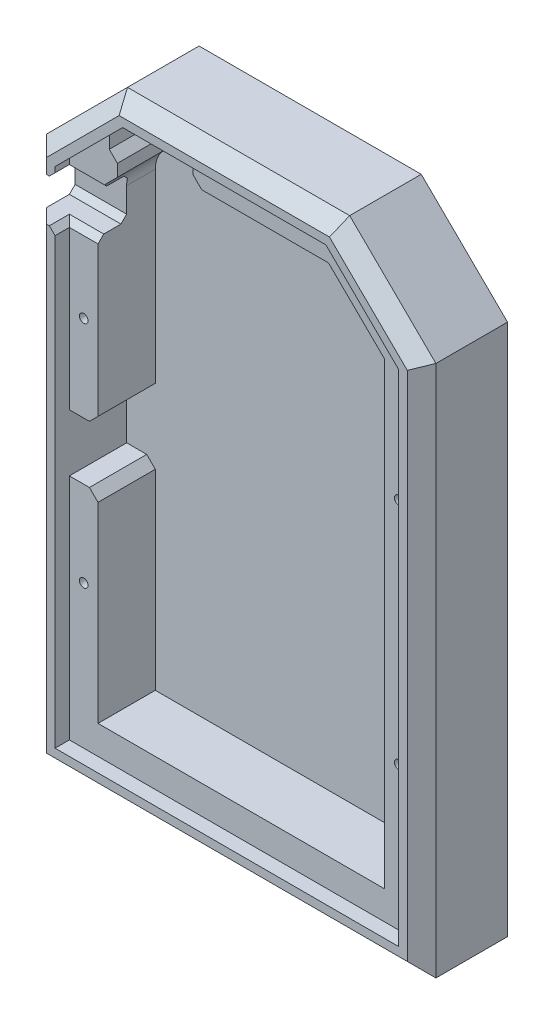
SolidWorks part; units mm, degrees
ref_plane "Front Plane" through (0, 0, 0) normal (1, 0, 0) x (0, 1, 0)
ref_plane "Top Plane" through (0, 0, 0) normal (0, 0, 1) x (0, 1, 0)
ref_plane "Right Plane" through (0, 0, 0) normal (0, 1, 0) x (-1, 0, 0)
sketch "Sketch1" plane through (0, 0, 0) normal (0, 0, 1) x (0, 1, 0)
  line L0 (175.9, 0) -> (199.5, -23.6)
  line L1 (0, 0) -> (175.9, 0)
  line L2 (0, 0) -> (0, -120)
  line L3 (0, -120) -> (174.5, -120)
  line L4 (199.5, -23.6) -> (199.5, -94.6)
  line L5 (199.5, -23.6) -> (199.5, -94.6)
  line L6 (199.5, -94.6) -> (174.5, -120)
  line L7 (205.2016, -100.2118) -> (177.851, -128)
  line L8 (-8, -128) -> (177.851, -128)
  line L9 (-8, 8) -> (-8, -128)
  line L10 (-8, 8) -> (179.2137, 8)
  line L11 (179.2137, 8) -> (205.1569, -17.9431)
  line L12 (207.5, -23.6) -> (207.5, -94.6)
  line L13 (207.5, -23.6) -> (207.5, -94.6)
  line L14 (177.851, -128) -> (207.5, -97.8766)
  line L15 (207.5, -97.8766) -> (207.5, -23.6)
  line L16 (179.2137, 8) -> (200.8013, -13.5876)
  line L17 (200.8013, -13.5876) -> (207.5, -20.2863)
  line L18 (207.5, -20.2863) -> (207.5, -23.6)
  line L19 (189.5, -90.5043) -> (170.3113, -110)
  line L20 (10, -110) -> (170.3113, -110)
  line L21 (10, -10) -> (10, -110)
  line L22 (10, -10) -> (171.7579, -10)
  line L23 (171.7579, -10) -> (189.5, -27.7421)
  line L24 (189.5, -27.7421) -> (189.5, -90.5043)
  line L25 (79.85, 0) -> (79.85, -12.2271)
  line L26 (192.373, -87.5853) -> (170.3113, -110) construction
  line L27 (189.5, -23.6) -> (189.5, -94.6) construction
  line L28 (171.7579, -10) -> (192.4289, -30.6711) construction
  line L29 (79.85, -12.2271) -> (99.85, -12.2271)
  line L30 (99.85, -12.2271) -> (99.85, 0)
  line L31 (79.85, 0) -> (99.85, 0)
  line L32 (187.7, -11.8) -> (169.825, -29.675)
  line L33 (169.825, -29.675) -> (183.3393, -43.1892)
  line L34 (183.3393, -43.1892) -> (199.5, -43.1892)
  line L35 (199.5, -43.1892) -> (199.5, -23.6)
  line L36 (50, -5) -> (50, -115) construction
  line L37 (130, -5) -> (130, -115) construction
  line L38 (130, -115) -> (50, -115) construction
  circle A0 centre (50, -5) radius 1.5
  circle A1 centre (130, -5) radius 1.5
  circle A2 centre (50, -115) radius 1.5
  circle A3 centre (130, -115) radius 1.5
  dimension "D5" = 3
  dimension "D1" = 120
  dimension "D2" = 8
  dimension "D3" = 50
  dimension "D4" = 5
  dimension "D6" = 10
  dimension "D7" = 80
  dimension "D8" = 20
  dimension "D9" = 30.15
  dimension "D10" = 5
extrude "Boss-Extrude1" add sketch "Sketch1" along normal blind 5 contours L34 L33 L32 L23 L22 L30 L29 L25 L21 L20 L19 L24 | L34 L24 L19 L20 L21 L22 L25 L1 L2 L3 L6 L5 A3 A2 A0 | L18 L17 L11 L10 L9 L8 L7 L14 L15 L12 L4 L5 L6 L3 L2 L1 L0 | L24 L34 L4 L0 L32 L23 | L32 L0 L1 L30 L22 L23 A1 | L33 L34 L24 L23 L32 | L22 L30 L1 L25 | L29 L30 L22 L25 | A0 | A1 | A3 | A2 region at (5.7866, 143.9357, 0) region at (28.013, 192.3485, 0) region at (5, 89.85, 0) region at (60.5328, 96.7361, 0) region at (31.5918, 181.6671, 0) region at (5, 77.5219, 0) region at (11.1136, 89.85, 0) region at (112.3184, 189.7101, 0) region at (5, 50, 0) region at (5, 130, 0) region at (115, 50, 0) region at (115, 130, 0)
extrude "Boss-Extrude2" add sketch "Sketch1<3>" along normal blind 25 contours L34 L24 L19 L20 L21 L22 L25 L1 L2 L3 L6 L5 A3 A2 A0 | L32 L0 L1 L30 L22 L23 A1 | L18 L17 L11 L10 L9 L8 L7 L14 L15 L12 L4 L5 L6 L3 L2 L1 L0 region at (5.7866, 143.9357, 0) region at (5, 77.5219, 0) region at (112.3184, 189.7101, 0)
sketch "Sketch1<3>" plane through (0, 0, 0) normal (0, 0, 1) x (0, 1, 0) same geometry as "Sketch1"
extrude "Boss-Extrude3" add sketch "Sketch1<4>" along normal blind 5 from surface contours L18 L17 L11 L10 L9 L8 L7 L14 L15 L12 L4 L5 L6 L3 L2 L1 L0 region at (112.3184, 189.7101, 0) starting at face at (35.0824, 133.4141, 25)
sketch "Sketch1<4>" plane through (0, 0, 0) normal (0, 0, 1) x (0, 1, 0) same geometry as "Sketch1"
chamfer "Chamfer1" distance 5 angle 45 6 edges at (6.1431, 193.3569, 30) (59.0814, 207.5, 30) (112.9383, 192.6755, 30) (-8, 85.6069, 30) (60, -8, 30) (128, 84.9255, 30)
chamfer "Chamfer2" distance 3 angle 45 6 edges at (10, 79.85, 15) (10, 99.85, 15) (43.1892, 199.5, 15) (43.1892, 189.5, 15) (11.8, 187.7, 15) (18.8711, 180.6289, 15)
sketch "Sketch2" plane through (0, 0, 30) normal (0, 0, 1) x (1, 0, 0)
  line L0 (-9.2398, 157) -> (15.9923, 157)
  line L3 (15.9923, 157) -> (15.9923, 172)
  line L5 (15.9923, 172) -> (-9.2398, 172)
  line L6 (-9.2398, 172) -> (-9.2398, 157)
  circle A0 centre (5, 130) radius 1.5 construction
  circle A1 centre (5, 130) radius 1.5
  point P5 (0, 0)
  point P6 (0, 0)
  point P12 (0, 0)
  point P14 (0, 0)
  dimension "D1" = 27
  dimension "D2" = 15
extrude "Cut-Extrude1" cut sketch "Sketch2" against normal blind 15 and the other way blind 5
chamfer "Chamfer3" distance 2 angle 45 6 edges at (1.1211, 172, 15) (1, 157, 15) (0, 172, 27.5) (5.1211, 172, 25) (0, 157, 27.5) (5, 157, 25)
fillet "Fillet1" radius 10 1 edges at (10, 171.7579, 10.8789)
